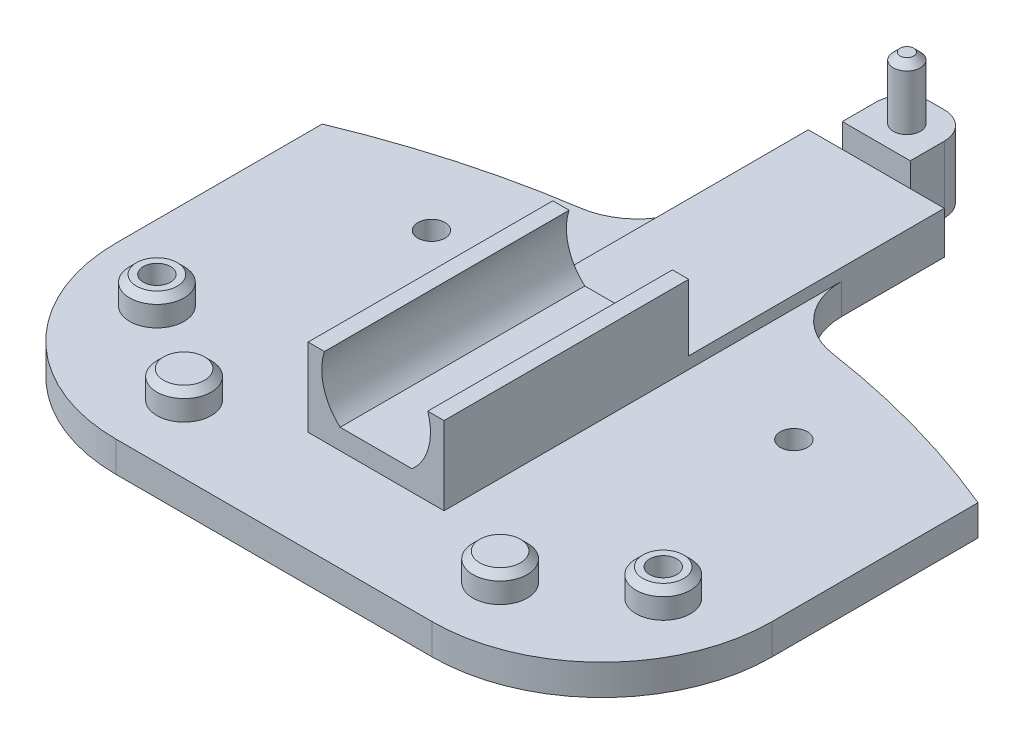
SolidWorks part; units mm, degrees
ref_plane "Front Plane" through (0, 0, 0) normal (0, 0, 1) x (1, 0, 0)
ref_plane "Top Plane" through (0, 0, 0) normal (0, 1, 0) x (1, 0, 0)
ref_plane "Right Plane" through (0, 0, 0) normal (1, 0, 0) x (0, 0, -1)
sketch "Sketch1" plane through (0, 0, 0) normal (0, 1, 0) x (1, 0, 0)
  line L1 (0, 0) -> (96.5, 0)
  line L2 (0, 0) -> (0, -110)
  line L3 (0, -110) -> (96.5, -110)
  line L4 (96.5, 0) -> (96.5, -110)
  dimension "D1" = 110
  dimension "D2" = 96.5
extrude "Boss-Extrude1" add sketch "Sketch1" along normal blind 4.5
sketch "Sketch2" plane through (0, 4.5, 0) normal (0, 1, 0) x (1, 0, 0)
  line L0 (48.25, -8.0497) -> (48.25, 8.0497) construction
  line L1 (85.5, -100) -> (85.5, -90) construction
  line L2 (-30.7875, -55) -> (30.7875, -55) construction
  line L3 (71.5, -100) -> (85.5, -100) construction
  line L4 (0, 0) -> (25, 0) construction
  line L5 (96.5, 0) -> (0, 0) construction
  line L6 (25, 0) -> (25, -100) construction
  line L7 (25, -100) -> (11, -100) construction
  line L8 (11, -100) -> (11, -90) construction
  line L9 (71.5, 0) -> (71.5, -100) construction
  line L10 (96.5, 0) -> (71.5, 0) construction
  line L11 (0, 0) -> (0, -110) construction
  circle A0 centre (25, -100) radius 4
  circle A1 centre (11, -90) radius 4
  circle A2 centre (85.5, -90) radius 4
  circle A3 centre (71.5, -100) radius 4
  point P3 (48.25, 0)
  point P6 (0, -55)
  dimension "D3" = 8
  dimension "D5" = 8
  dimension "D1" = 25
  dimension "D2" = 100
  dimension "D4" = 14
  dimension "D6" = 10
  dimension "D7" = 48.25
extrude "Boss-Extrude2" add sketch "Sketch2" along normal blind 4 contours A0 | A3 region at (25, 4.5, 100) region at (71.5, 4.5, 100)
sketch "Sketch3" plane through (0, 4.5, 0) normal (0, 1, 0) x (1, 0, 0)
  line L0 (71.5, -100) -> (71.5, -12.4) construction
  line L1 (48.25, 0) -> (48.25, -50000) construction
  line L2 (96.5, 0) -> (0, 0) construction
  line L3 (71.5, -12.4) -> (48.25, -12.4) construction
  line L4 (48.25, -12.4) -> (48.25, -14.9) construction
  circle A0 centre (48.25, -16.9) radius 2
  point P7 (48.25, 0)
  dimension "D2" = 4
  dimension "D1" = 87.6
  dimension "D3" = 2.5
extrude "Boss-Extrude3" add sketch "Sketch3" along normal blind 14.4
sketch "Sketch4" plane through (0, 4.5, 0) normal (0, 1, 0) x (1, 0, 0)
  line L0 (48.25, -18.9) -> (48.25, -21.4) construction
  line L1 (48.25, -14.9) -> (48.25, -12.4) construction
  line L2 (48.25, -21.4) -> (38.25, -21.4)
  line L3 (48.25, -21.4) -> (48.25, -59)
  line L4 (48.25, -59) -> (38.25, -59)
  line L5 (38.25, -21.4) -> (38.25, -59)
  line L6 (48.25, -21.4) -> (38.25, -59) construction
  line L7 (48.25, -59) -> (38.25, -21.4) construction
  line L8 (48.25, -59) -> (58.25, -59)
  line L9 (48.25, -59) -> (48.25, -23)
  line L12 (48.25, -21.4) -> (53.25, -21.4)
  line L13 (53.25, -21.4) -> (53.25, -16.4)
  line L14 (38.25, -59) -> (58.25, -59)
  line L15 (38.25, -59) -> (38.25, -95)
  line L16 (38.25, -95) -> (58.25, -95)
  line L17 (58.25, -59) -> (58.25, -95)
  line L18 (38.25, -59) -> (58.25, -95) construction
  line L19 (38.25, -95) -> (58.25, -59) construction
  line L21 (48.25, -12.4) -> (47.25, -12.4)
  line L22 (48.25, -12.4) -> (48.25, -21.4)
  line L23 (48.25, -21.4) -> (43.25, -21.4)
  line L24 (43.25, -16.4) -> (43.25, -21.4)
  line L25 (48.25, -12.4) -> (43.25, -21.4) construction
  line L26 (48.25, -21.4) -> (43.25, -12.4) construction
  line L27 (48.25, -12.4) -> (49.25, -12.4)
  line L28 (48.25, -12.4) -> (48.25, -23)
  line L31 (48.25, -21.4) -> (58.25, -21.4)
  line L32 (48.25, -21.4) -> (48.25, -59)
  line L33 (48.25, -59) -> (58.25, -59)
  line L34 (58.25, -21.4) -> (58.25, -59)
  line L35 (48.25, -21.4) -> (58.25, -59) construction
  line L36 (48.25, -59) -> (58.25, -21.4) construction
  circle A0 centre (48.25, -16.9) radius 2 construction
  circle A1 centre (48.25, -16.9) radius 2 construction
  arc A2 (49.25, -12.4) -> (53.25, -16.4) centre (49.25, -16.4) cw
  arc A3 (43.25, -16.4) -> (47.25, -12.4) centre (47.25, -16.4) cw
  point P8 (43.25, -40.2)
  point P16 (48.25, -77)
  point P24 (45.75, -16.9)
  point P28 (50.75, -17.7)
  point P35 (53.25, -40.2)
  circle M2 centre (48.25, -16.9) radius 2
  dimension "D3" = 4
  dimension "D1" = 2.5
  dimension "D2" = 2.5
  dimension "D4" = 37.6
  dimension "D5" = 36
  dimension "D6" = 20
extrude "Boss-Extrude4" add sketch "Sketch4" along normal blind 1.75 contours L2 L5 L4 L3 | L8 L3 region at (43.25, 4.5, 40.2) region at (53.25, 4.5, 40.2)
extrude "Boss-Extrude5" add sketch "Sketch4<3>" along normal blind 11.5 contours L17 L8 L4 L15 L16 region at (48.25, 4.5, 77)
sketch "Sketch4<3>" plane through (0, 4.5, 0) normal (0, 1, 0) x (1, 0, 0) same geometry as "Sketch4"
extrude "Boss-Extrude6" add sketch "Sketch4<5>" along normal blind 5.3 contours A3 L24 L2 L22 L21 M2 | A2 L27 L22 M2 region at (50.8877, 4.5, 17.251) region at (45.6123, 4.5, 17.251)
sketch "Sketch4<5>" plane through (0, 4.5, 0) normal (0, 1, 0) x (1, 0, 0) same geometry as "Sketch4"
chamfer "Chamfer2" distance 1 angle 45 1 edges at (48.25, 18.9, 18.9)
sketch "Sketch9" plane through (0, 0, 59) normal (0, 0, -1) x (-1, 0, 0)
  line L0 (-58.25, 6.25) -> (-58.25, 7.5) construction
  line L4 (-58.25, 7.5) -> (-50058.25, 7.5) construction
  line L7 (-64.0844, 7.5) -> (-64.0844, 19.5) construction
  line L10 (-64.0844, 19.5) -> (-50064.0844, 19.5) construction
  line L11 (-64.0844, 13.5) -> (49935.9156, 13.5) construction
  line L12 (-58.25, 4.5) -> (-38.25, 4.5) construction
  line L13 (-48.25, 4.5) -> (-48.25, 50004.5) construction
  line L14 (-58.25, 16) -> (-58.25, 6.25) construction
  line L16 (-53.5415, 7.5) -> (-42.9585, 7.5)
  circle A0 centre (-48.25, 13.5) radius 8
  point P15 (-64.0844, 13.5)
  point P22 (-48.25, 4.5)
  line M5 (-38.25, 16) -> (-58.25, 16)
  dimension "D3" = 16
  dimension "D1" = 1.25
  dimension "D2" = 12
extrude "Cut-Extrude6" cut sketch "Sketch9" against normal through all contours A0 L16 M5 region at (48.25, 11.9541, 59)
chamfer "Chamfer3" distance 1 angle 45 2 edges at (71.5, 8.5, 104) (25, 8.5, 104)
extrude "Boss-Extrude8" add sketch "Sketch2<4>" along normal blind 4 contours A1 | A2 region at (11, 4.5, 90) region at (85.5, 4.5, 90)
sketch "Sketch2<4>" plane through (0, 4.5, 0) normal (0, 1, 0) x (1, 0, 0) same geometry as "Sketch2"
sketch "Sketch20" plane through (0, 4.5, 0) normal (0, 1, 0) x (1, 0, 0)
  line L0 (0, 0) -> (96.5, 0)
  line L1 (96.5, 0) -> (96.5, -54.6877)
  line L2 (0, 0) -> (0, -54.6877)
  line L3 (38.25, -45.4006) -> (38.25, -21.4)
  line L4 (38.25, -21.4) -> (43.25, -21.4)
  line L5 (43.25, -21.4) -> (43.25, -16.4)
  line L6 (47.25, -12.4) -> (49.25, -12.4)
  line L7 (53.25, -16.4) -> (53.25, -21.4)
  line L8 (53.25, -21.4) -> (58.25, -21.4)
  line L9 (58.25, -21.4) -> (58.25, -45.4006)
  arc A2 (0, -54.6877) -> (38.25, -45.4006) centre (48.25, -170) cw
  arc A3 (58.25, -45.4006) -> (96.5, -54.6877) centre (48.25, -170) cw
  arc A4 (43.25, -16.4) -> (47.25, -12.4) centre (47.25, -16.4) cw
  arc A5 (49.25, -12.4) -> (53.25, -16.4) centre (49.25, -16.4) cw
  circle A6 centre (48.25, -170) radius 125 construction
  point P6 (0, 0)
  point P7 (0, 0)
  point P8 (0, 0)
  point P10 (0, 0)
  point P11 (0, -54.6877)
  point P36 (0, 0)
  point P38 (0, 0)
  point P39 (0, 0)
extrude "Cut-Extrude10" cut sketch "Sketch20" against normal through all
fillet "Fillet1" radius 10 2 edges at (58.25, 2.25, 45.4006) (38.25, 2.25, 45.4006)
sketch "Sketch21" plane through (0, 4.5, 0) normal (0, 1, 0) x (1, 0, 0)
  line L0 (38.25, -21.4) -> (38.25, -59) construction
  line L1 (18.7572, -48.5291) -> (21.5885, -60.1903)
  line L2 (48.25, -80) -> (48.25, 49920) construction
  circle A0 centre (21.5885, -60.1903) radius 2
  arc A1 (0, -54.6877) -> (38.25, -45.4006) centre (48.25, -170) cw
  circle A2 centre (48.25, -170) radius 125 construction
  circle A3 centre (74.9115, -60.1903) radius 2
  dimension "D1" = 4
  dimension "D2" = 12
extrude "Cut-Extrude11" cut sketch "Sketch21" against normal through all contours A0 | A3 region at (20.3873, 4.5, 61.7181) region at (74.9115, 4.5, 60.1903)
chamfer "Chamfer4" distance 1 angle 45 2 edges at (85.5, 8.5, 94) (11, 8.5, 94)
sketch "Sketch22" plane through (0, 8.5, 0) normal (0, 1, 0) x (1, 0, 0)
  circle A0 centre (11, -90) radius 2
  circle A1 centre (85.5, -90) radius 2
  dimension "D1" = 4
  dimension "D2" = 4
extrude "Cut-Extrude12" cut sketch "Sketch22" against normal through all
fillet "Fillet2" radius 25 2 edges at (96.5, 2.25, 110) (0, 2.25, 110)
